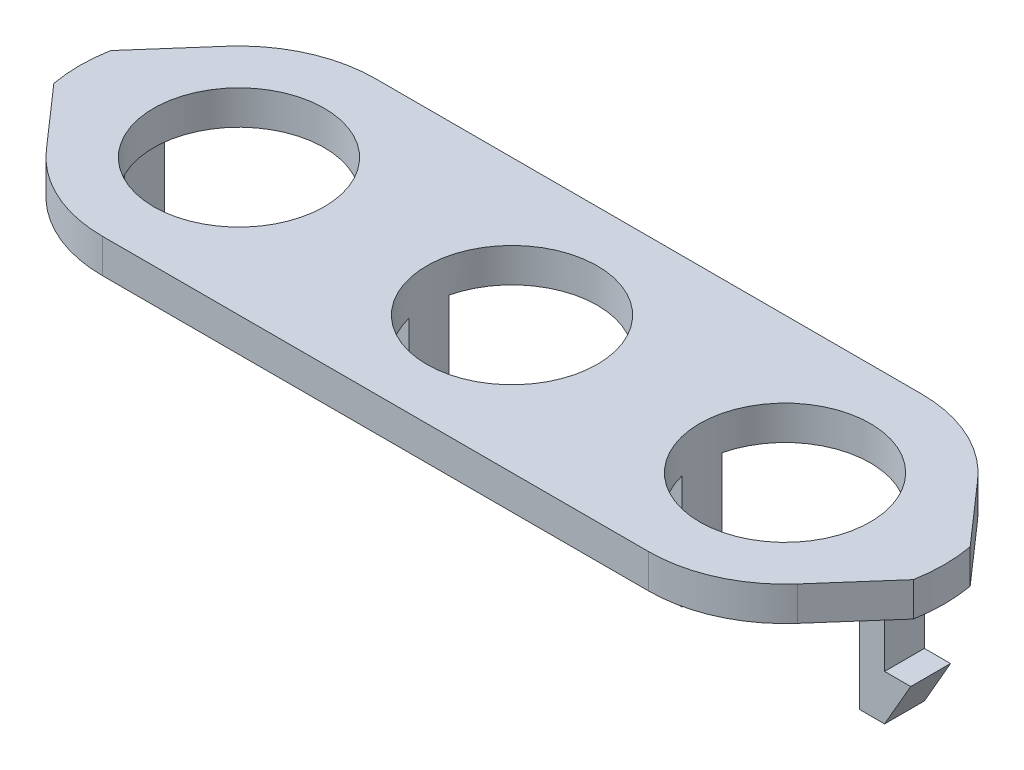
SolidWorks part; units mm, degrees
ref_plane "Front Plane" through (0, 0, 0) normal (0, 0, 1) x (1, 0, 0)
ref_plane "Top Plane" through (0, 0, 0) normal (0, 1, 0) x (1, 0, 0)
ref_plane "Right Plane" through (0, 0, 0) normal (1, 0, 0) x (0, 0, -1)
sketch "Sketch1" plane through (0, 0, 0) normal (0, 1, 0) x (1, 0, 0)
  line L0 (37.775, -2.5) -> (33.0167, -7.9183)
  line L1 (37.775, 2.5) -> (33.0167, 7.9183)
  line L2 (24, 12) -> (-24, 12)
  line L3 (-37.775, -2.5) -> (-33.0167, -7.9183)
  line L4 (-12, 9.4167) -> (-2.8534, 11.6558)
  line L5 (-12, -9.4167) -> (-2.8534, -11.6558)
  line L6 (-12, -9.4167) -> (-21.1466, -11.6558)
  line L7 (-12, 9.4167) -> (-21.1466, 11.6558)
  line L8 (-37.775, 2.5) -> (-33.0167, 7.9183)
  line L9 (12, -9.4167) -> (2.8534, -11.6558)
  line L10 (12, -9.4167) -> (21.1466, -11.6558)
  line L11 (12, 9.4167) -> (21.1466, 11.6558)
  line L12 (12, 9.4167) -> (2.8534, 11.6558)
  line L13 (24, -12) -> (-24, -12)
  arc A0 (-37.775, -2.5) -> (-37.775, 2.5) centre (-24, 0) cw
  arc A1 (-2.8534, -11.6558) -> (2.8534, -11.6558) centre (0, 0) ccw
  arc A2 (21.1466, 11.6558) -> (33.0167, 7.9183) centre (24, 0) cw
  circle A3 centre (24, 0) radius 7.5
  arc A4 (-21.1466, -11.6558) -> (-33.0167, -7.9183) centre (-24, 0) cw
  circle A5 centre (-24, 0) radius 7.5
  arc A6 (2.8534, 11.6558) -> (-2.8534, 11.6558) centre (0, 0) ccw
  circle A7 centre (0, 0) radius 7.5
  arc A8 (37.775, -2.5) -> (37.775, 2.5) centre (24, 0) ccw
  arc A9 (33.0167, -7.9183) -> (21.1466, -11.6558) centre (24, 0) cw
  arc A10 (-33.0167, 7.9183) -> (-21.1466, 11.6558) centre (-24, 0) cw
  dimension "D2" = 24
  dimension "D3" = 15
  dimension "D4" = 15
  dimension "D5" = 15
extrude "Boss-Extrude2" add sketch "Sketch1" along normal blind 3 contours A10 L8 A0 L3 A4 L6 L5 A1 L9 L10 A9 L0 A8 L1 A2 L11 L12 A6 L4 L7 A7 A5 A3 | L6 A4 L13 A1 L5 | L13 A9 L10 L9 A1 | A6 L12 L11 A2 L2 | L2 A10 L7 L4 A6 region at (34.797, 0, 4.6833) region at (12, 0, 11.1437) region at (-12, 0, 11.1437) region at (12, 0, -11.1437) region at (-12, 0, -11.1437)
sketch "Sketch2" plane through (0, 0, 0) normal (0, -1, 0) x (1, 0, 0)
  line L0 (16.707, 1.75) -> (7.293, 1.75)
  line L1 (16.707, -1.75) -> (7.293, -1.75)
  line L2 (-34.5, 1.75) -> (-34.5, 0)
  line L3 (-7.293, -1.75) -> (-16.707, -1.75)
  line L4 (-34.5, -1.75) -> (-34.5, 0)
  line L5 (-7.293, 1.75) -> (-16.707, 1.75)
  line L6 (-31.293, 1.75) -> (-34.5, 1.75)
  line L7 (-31.293, -1.75) -> (-34.5, -1.75)
  line L8 (34.5, 1.75) -> (34.5, 0)
  line L9 (34.5, -1.75) -> (34.5, 0)
  line L14 (34.5, -1.75) -> (31.293, -1.75)
  line L15 (34.5, 1.75) -> (31.293, 1.75)
  circle A0 centre (-24, 0) radius 7.5 construction
  arc A1 (31.293, -1.75) -> (31.293, 1.75) centre (24, 0) ccw
  arc A3 (-7.293, 1.75) -> (-7.293, -1.75) centre (0, 0) ccw
  circle A4 centre (0, 0) radius 7.5 construction
  circle A5 centre (24, 0) radius 7.5 construction
  arc A6 (-16.707, -1.75) -> (-16.707, 1.75) centre (-24, 0) ccw
  arc A7 (7.293, -1.75) -> (7.293, 1.75) centre (0, 0) ccw
  arc A8 (16.707, 1.75) -> (16.707, -1.75) centre (24, 0) ccw
  arc A9 (-31.293, 1.75) -> (-31.293, -1.75) centre (-24, 0) ccw
extrude "Boss-Extrude4" add sketch "Sketch2" along normal blind 10
sketch "Sketch4" plane through (0, 0, -1.75) normal (0, 0, -1) x (-1, 0, 0)
  line L0 (34.5, -10) -> (34.5, -6)
  line L1 (34.5, -10) -> (34.5, 0) construction
  line L2 (34.5, -6) -> (36.8, -6)
  line L3 (34.5, -10) -> (36.8, -6)
  line L5 (-34.5, -10) -> (-36.8, -6)
  line L6 (-34.5, -6) -> (-36.8, -6)
  line L7 (-34.5, -10) -> (-34.5, -6)
  dimension "D1" = 4
  dimension "D2" = 2.3
extrude "Boss-Extrude5" add sketch "Sketch4" against normal up to surface (3.5 mm away) up to face at (-32.4956, -6.25, 1.75)
sketch "Sketch5" plane through (0, -10, 0) normal (0, -1, 0) x (1, 0, 0)
  line L0 (-31.293, 1.75) -> (-32.293, 1.75)
  line L1 (-31.293, 1.75) -> (-34.5, 1.75) construction
  line L2 (-32.293, 1.75) -> (-32.293, -1.75)
  line L3 (-34.5, 1.75) -> (-34.5, -1.75)
  line L4 (-34.5, -1.75) -> (-31.293, -1.75)
  line L5 (-31.293, 1.75) -> (-34.5, 1.75)
  line L6 (-34.5, -1.75) -> (-31.293, -1.75) construction
  line L7 (-31.293, -1.75) -> (-32.293, -1.75)
  line L8 (0, 0) -> (0, 8.4881)
  line L9 (31.293, -1.75) -> (32.293, -1.75)
  line L10 (32.293, 1.75) -> (32.293, -1.75)
  line L11 (31.293, 1.75) -> (32.293, 1.75)
  arc A1 (-31.293, 1.75) -> (-31.293, -1.75) centre (-24, 0) ccw
  arc A2 (-31.293, 1.75) -> (-31.293, -1.75) centre (-24, 0) ccw
  arc A3 (31.293, 1.75) -> (31.293, -1.75) centre (24, 0) cw
  line M6 (-34.5, -1.75) -> (-31.293, -1.75)
  arc M7 (-31.293, -1.75) -> (-31.293, 1.75) centre (-24, 0) cw
  line M8 (-31.293, 1.75) -> (-34.5, 1.75)
  dimension "D2" = 1
  dimension "D1" = 0
extrude "Cut-Extrude1" cut sketch "Sketch5" against normal up to surface (10 mm away) contours L2 M8 M6 M7 | L10 L9 A3 L11 region at (-31.86, -10, 0) up to face at (0, 0, 0)
